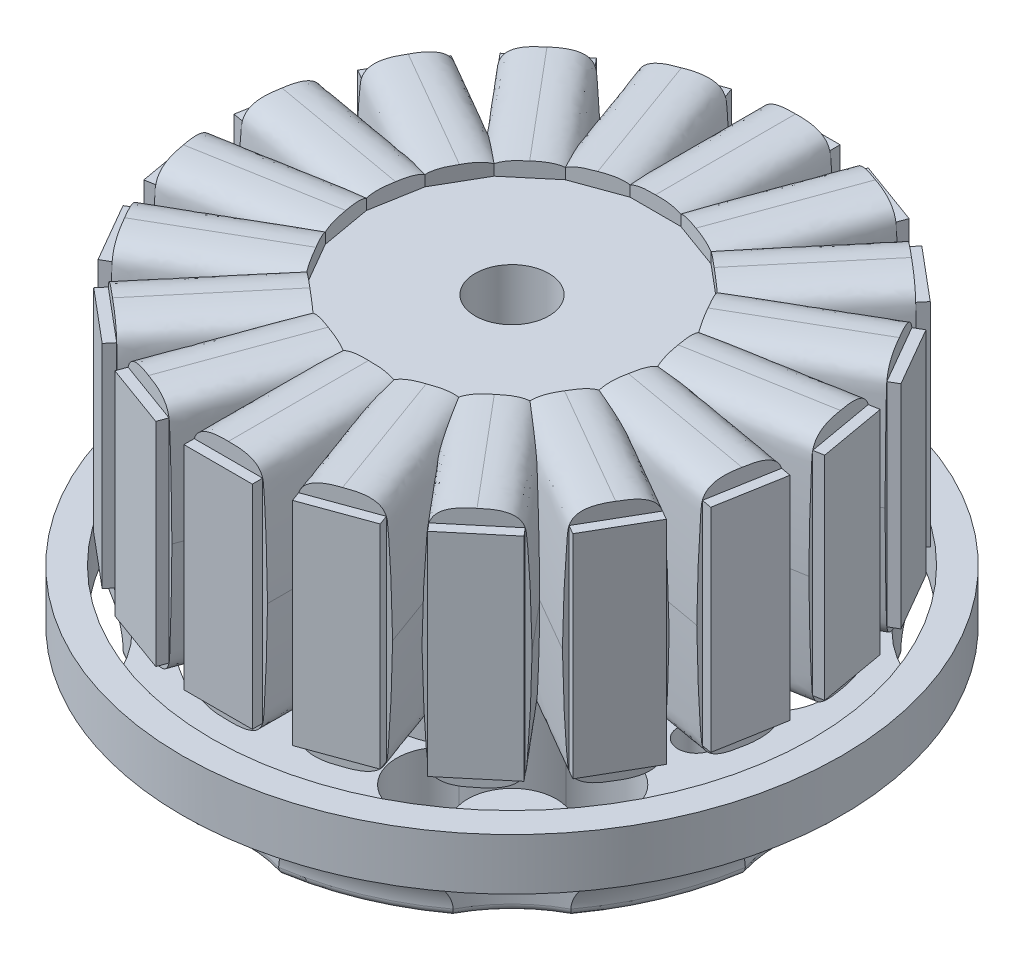
SolidWorks part; units mm, degrees
ref_plane "Front Plane" through (0, 0, 0) normal (0, 0, 1) x (1, 0, 0)
ref_plane "Top Plane" through (0, 0, 0) normal (0, 1, 0) x (1, 0, 0)
ref_plane "Right Plane" through (0, 0, 0) normal (1, 0, 0) x (0, 0, -1)
sketch "Sketch1" plane through (0, 0, 0) normal (0, 1, 0) x (1, 0, 0)
  circle A0 centre (0, 0) radius 22.36
  dimension "D1" = 44.72
extrude "Boss-Extrude1" add sketch "Sketch1" against normal blind 7.5
sketch "Sketch4" plane through (0, 0, 0) normal (0, 0, 1) x (1, 0, 0)
  line L0 (-22.36, 0) -> (-22.36, -7.5) construction
  line L1 (0, 0) -> (0, -7.5) construction
  line L2 (-22.36, -7.5) -> (22.36, -7.5) construction
  circle A0 centre (-22.36, -7) radius 3.5
  point P0 (-22.36, -3.5)
  dimension "D2" = 7
  dimension "D1" = 3.5
revolve "Cut-Revolve1" cut sketch "Sketch4" angle 360 about L1
sketch "Sketch6" plane through (0, 0, 0) normal (0, 1, 0) x (1, 0, 0)
  circle A0 centre (0, 0) radius 20.36
  circle A1 centre (0, 0) radius 22.36 construction
  dimension "D1" = 2
extrude "Cut-Extrude3" cut sketch "Sketch6" against normal offset from surface (3.9 mm away) 3.6 up to face at (0, -7.5, -18.8959)
sketch "Sketch7" plane through (0, -3.9, 0) normal (0, 1, 0) x (1, 0, 0)
  circle A0 centre (0, 0) radius 10
  dimension "D1" = 20
extrude "Boss-Extrude2" add sketch "Sketch7" along normal blind 20.8
sketch "Sketch9" plane through (0, 16.9, 0) normal (0, 1, 0) x (1, 0, 0)
  line L0 (0, 0) -> (0, 30.8814) construction
  line L2 (-2.32, 19.93) -> (2.32, 19.93)
  line L3 (-2.32, 19.93) -> (-2.32, 19.23)
  line L4 (-2.32, 19.23) -> (-0.3439, 19.23)
  line L5 (2.32, 19.93) -> (2.32, 19.23)
  line L6 (-2.32, 19.93) -> (2.32, 19.23) construction
  line L7 (-2.32, 19.23) -> (2.32, 19.93) construction
  line L16 (16.0999, 11.9742) -> (15.4937, 11.6242)
  line L75 (0.3439, 19.23) -> (2.32, 19.23)
  line L77 (-0.35, 19.23) -> (-0.35, 9.9939)
  line L79 (0.35, 19.23) -> (0.35, 9.9939)
  line L133 (-19.3407, 1.0545) -> (-18.9986, 2.9946) [skipped]
  line L134 (-20.0301, 1.1761) -> (-19.2244, 5.7456) [skipped]
  line L135 (-19.2244, 5.7456) -> (-18.535, 5.624) [skipped]
  line L136 (-20.0301, 1.1761) -> (-19.3407, 1.0545) [skipped]
  line L137 (-18.4199, 7.9558) -> (-17.8137, 7.6058) [skipped]
  line L138 (-18.4199, 7.9558) -> (-16.0999, 11.9742) [skipped]
  line L139 (-16.0999, 11.9742) -> (-15.4937, 11.6242) [skipped]
  line L140 (-17.8137, 7.6058) -> (-16.8287, 9.3119) [skipped]
  line L141 (-14.588, 13.776) -> (-14.138, 13.2398) [skipped]
  line L142 (-14.138, 13.2398) -> (-12.6289, 14.5061) [skipped]
  line L143 (-14.588, 13.776) -> (-11.0335, 16.7585) [skipped]
  line L144 (-11.0335, 16.7585) -> (-10.5836, 16.2223) [skipped]
  line L145 (-8.7571, 17.2768) -> (-6.9059, 17.9506) [skipped]
  line L146 (-8.9965, 17.9346) -> (-4.6364, 19.5216) [skipped]
  line L147 (-4.6364, 19.5216) -> (-4.397, 18.8638) [skipped]
  line L148 (-8.9965, 17.9346) -> (-8.7571, 17.2768) [skipped]
  line L161 (4.397, 18.8638) -> (6.2482, 18.19) [skipped]
  line L162 (4.6364, 19.5216) -> (8.9965, 17.9346) [skipped]
  line L163 (11.0335, 16.7585) -> (10.5836, 16.2223) [skipped]
  line L164 (11.0335, 16.7585) -> (14.588, 13.776) [skipped]
  line L165 (16.0999, 11.9742) -> (18.4199, 7.9558) [skipped]
  line L166 (18.4199, 7.9558) -> (17.8137, 7.6058) [skipped]
  line L167 (15.4937, 11.6242) -> (16.4787, 9.9181) [skipped]
  line L168 (19.2244, 5.7456) -> (18.535, 5.624) [skipped]
  line L169 (19.2244, 5.7456) -> (20.0301, 1.1761) [skipped]
  line L170 (19.3407, -1.0545) -> (18.9986, -2.9946) [skipped]
  line L171 (20.0301, -1.1761) -> (19.2244, -5.7456) [skipped]
  line L172 (19.2244, -5.7456) -> (18.535, -5.624) [skipped]
  line L187 (14.138, -13.2398) -> (12.6289, -14.5061) [skipped]
  line L188 (14.588, -13.776) -> (11.0335, -16.7585) [skipped]
  line L189 (18.4199, -7.9558) -> (16.0999, -11.9742) [skipped]
  line L190 (17.8137, -7.6058) -> (16.8287, -9.3119) [skipped]
  line L191 (16.0999, -11.9742) -> (15.4937, -11.6242) [skipped]
  line L192 (2.32, -19.23) -> (-2.32, -19.23) [skipped]
  line L193 (-2.32, -19.93) -> (-2.32, -19.23) [skipped]
  line L194 (-4.397, -18.8638) -> (-8.7571, -17.2768) [skipped]
  line L195 (-4.6364, -19.5216) -> (-8.9965, -17.9346) [skipped]
  line L196 (-11.0335, -16.7585) -> (-10.5836, -16.2223) [skipped]
  line L197 (-10.5836, -16.2223) -> (-14.138, -13.2398) [skipped]
  line L198 (-16.0999, -11.9742) -> (-18.4199, -7.9558) [skipped]
  line L199 (-19.2244, -5.7456) -> (-20.0301, -1.1761) [skipped]
  line L200 (-20.0301, -1.1761) -> (-19.3407, -1.0545) [skipped]
  line L201 (-18.535, -5.624) -> (-18.8771, -3.6839) [skipped]
  line L202 (-18.4199, -7.9558) -> (-17.8137, -7.6058) [skipped]
  line L203 (-15.4937, -11.6242) -> (-16.4787, -9.9181) [skipped]
  line L204 (-16.0999, -11.9742) -> (-15.4937, -11.6242) [skipped]
  line L205 (-14.588, -13.776) -> (-14.138, -13.2398) [skipped]
  line L206 (-11.0335, -16.7585) -> (-14.588, -13.776) [skipped]
  line L207 (-8.9965, -17.9346) -> (-8.7571, -17.2768) [skipped]
  line L208 (-19.2244, -5.7456) -> (-18.535, -5.624) [skipped]
  line L209 (-4.6364, -19.5216) -> (-4.397, -18.8638) [skipped]
  line L210 (2.32, -19.93) -> (-2.32, -19.93) [skipped]
  line L211 (2.32, -19.93) -> (2.32, -19.23) [skipped]
  line L212 (8.9965, -17.9346) -> (4.6364, -19.5216) [skipped]
  line L213 (8.7571, -17.2768) -> (4.397, -18.8638) [skipped]
  line L214 (4.7854, -19.9309) -> (4.397, -18.8638) [skipped]
  line L215 (11.0335, -16.7585) -> (10.5836, -16.2223) [skipped]
  line L216 (8.9965, -17.9346) -> (8.7571, -17.2768) [skipped]
  line L217 (14.588, -13.776) -> (14.138, -13.2398) [skipped]
  line L218 (18.4199, -7.9558) -> (17.8137, -7.6058) [skipped]
  line L219 (20.0301, -1.1761) -> (19.3407, -1.0545) [skipped]
  line L220 (20.0301, 1.1761) -> (19.3407, 1.0545) [skipped]
  line L221 (18.535, 5.624) -> (18.8771, 3.6839) [skipped]
  line L222 (4.6364, 19.5216) -> (4.397, 18.8638) [skipped]
  line L223 (8.9965, 17.9346) -> (8.7571, 17.2768) [skipped]
  line L224 (10.5836, 16.2223) -> (12.0927, 14.956) [skipped]
  line L225 (14.588, 13.776) -> (14.138, 13.2398) [skipped]
  arc A2 (0.35, 9.9939) -> (-0.35, 9.9939) centre (0, 0) ccw
  point P3 (0, 19.58)
  point P10 (0, 12.4867)
  point P79 (0, 0)
  point P156 (0, 0)
  dimension "D1" = 0.7
  dimension "D2" = 4.64
  dimension "D3" = 19.58
  dimension "D4" = 18
extrude "Boss-Extrude3" add sketch "Sketch9" against normal offset from surface (15.4 mm away) 1.5 up to face at (0, 0, 20.36)
pattern_circular "CirPattern1" count 18 over 360 about axis through (0, 0, 0) along (0, 1, 0) of "Boss-Extrude3"
sketch "Sketch10" plane through (0, 16.9, 0) normal (0, 1, 0) x (1, 0, 0)
  circle A0 centre (0, 0) radius 24.3732
extrude "Cut-Extrude4" cut sketch "Sketch10" against normal blind 1
sketch "Sketch11" plane through (0, -7.5, 0) normal (0, -1, 0) x (1, 0, 0)
  circle A0 centre (0, 0) radius 8
  dimension "D1" = 16
extrude "Cut-Extrude5" cut sketch "Sketch11" against normal blind 0.2
sketch "Sketch12" plane through (0, -7.3, 0) normal (0, -1, 0) x (-1, 0, 0)
  circle A0 centre (0, 0) radius 3.75
  circle A1 centre (0, 0) radius 2.5
  dimension "D1" = 7.5
  dimension "D2" = 5
extrude "Boss-Extrude4" add sketch "Sketch12" along normal blind 0.2
sketch "Sketch13" plane through (0, -7.3, 0) normal (0, -1, 0) x (1, 0, 0)
  circle A0 centre (0, 0) radius 2.5
extrude "Cut-Extrude6" cut sketch "Sketch13" against normal blind 41.2
sketch "Sketch14" plane through (0, -7.5, 0) normal (0, -1, 0) x (-1, 0, 0)
  line L0 (0, 0) -> (0, -25.6549) construction
  line L1 (0, 0) -> (-22.5396, -22.5396) construction
  line L2 (0, 0) -> (-26.5501, 0) construction
  circle A0 centre (0, -12.5) radius 1.25
  circle A1 centre (-12.5, 0) radius 1.25
  circle A2 centre (0, 12.5) radius 1.25
  circle A3 centre (12.5, 0) radius 1.25
  circle A4 centre (-11.3137, -11.3137) radius 1
  circle A5 centre (-4.1411, 15.4548) radius 1
  circle A6 centre (15.4548, -4.1411) radius 1
  circle A7 centre (0, 0) radius 22.36 construction
  circle A8 centre (-27.861, 0) radius 9.6379
  circle A9 centre (-19.7007, 19.7007) radius 9.6379
  circle A10 centre (0, 27.861) radius 9.6379
  circle A11 centre (19.7007, 19.7007) radius 9.6379
  circle A12 centre (27.861, 0) radius 9.6379
  circle A13 centre (19.7007, -19.7007) radius 9.6379
  circle A14 centre (0, -27.861) radius 9.6379
  circle A15 centre (-19.7007, -19.7007) radius 9.6379
  point P14 (0, 0)
  point P15 (-18.5, 0)
  point P16 (-19.8003, 10.3884)
  point P17 (-21.236, 7)
  point P22 (0, 0)
  point P24 (-21.236, -7)
  point P41 (0, 0)
  point P47 (0, 0)
  dimension "D1" = 2.5
  dimension "D5" = 2
  dimension "D2" = 12.5
  dimension "D4" = 45
  dimension "D6" = 16
  dimension "D8" = 18.5
  dimension "D9" = 7
  dimension "D10" = 7
  dimension "D12" = 3.68
  dimension "D3" = 4
  dimension "D7" = 3
  dimension "D11" = 8
extrude "Cut-Extrude7" cut sketch "Sketch14" against normal blind 4
sketch "Sketch15" plane through (0, -7.5, 0) normal (0, -1, 0) x (-1, 0, 0)
  line L0 (0, 0) -> (0, -18.223) construction
  line L1 (0, 0) -> (-11.3137, -11.3137) construction
  line L2 (0, 0) -> (-12.5, 0) construction
  line L3 (0, 0) -> (-4.1411, 15.4548) construction
  line L4 (0, 0) -> (10.251, -2.7468) construction
  line L5 (12.557, -3.3646) -> (15.4548, -4.1411) construction
  arc A0 (2.905, -18.6713) -> (-2.905, -18.6713) centre (0, -27.861) ccw construction
  arc A1 (-8.6571, -5.0055) -> (-5.0501, -8.6311) centre (0, 0) ccw
  arc A2 (10.6792, -3.4673) -> (8.6838, -4.959) centre (11.3975, -6.5086) ccw
  arc A3 (10.6792, -3.4673) -> (12.5009, -4.6651) centre (11.024, -4.9271) cw
  arc A4 (14.0447, 8.1737) -> (8.1473, 14.06) centre (0, 0) ccw
  arc A5 (12.5009, -4.6651) -> (13.5648, -6.4709) centre (15.4548, -4.1411) ccw
  arc A6 (4.9724, -8.6761) -> (8.0802, -14.0987) centre (6.5263, -11.3874) ccw
  arc A7 (8.0802, -14.0987) -> (13.9031, -8.4122) centre (0, 0) ccw
  circle A8 centre (0, -12.5) radius 3.55 construction
  arc A9 (-8.6761, 4.9724) -> (-14.0987, 8.0802) centre (-11.3874, 6.5263) cw
  circle A10 centre (0, 12.5) radius 3.55 construction
  circle A11 centre (-12.5, 0) radius 3.55 construction
  circle A12 centre (-4.1411, 15.4548) radius 3 construction
  arc A13 (-8.5024, -12.3608) -> (-12.3698, -8.5057) centre (-11.3137, -11.3137) ccw
  arc A14 (8.6429, 5.03) -> (14.0447, 8.1737) centre (11.3438, 6.6018) ccw
  arc A15 (8.1473, 14.06) -> (5.0137, 8.6523) centre (6.5805, 11.3562) ccw
  arc A16 (-8.6761, 4.9724) -> (-4.959, 8.6838) centre (0, 0) cw
  arc A17 (13.5648, -6.4709) -> (13.9031, -8.4122) centre (12.6198, -7.6357) cw
  arc A18 (-7.5291, -14.3207) -> (-5.0501, -8.6311) centre (-6.6283, -11.3284) ccw
  arc A19 (-8.6571, -5.0055) -> (-14.3152, -7.5929) centre (-11.3624, -6.5697) ccw
  arc A20 (-3.4673, 10.6792) -> (-4.959, 8.6838) centre (-6.5086, 11.3975) cw
  arc A21 (-3.4673, 10.6792) -> (-4.6651, 12.5009) centre (-4.9271, 11.024) ccw
  arc A22 (11.4264, -3.3838) -> (8.6838, -4.959) centre (11.3975, -6.5086) ccw
  arc A23 (-7.5291, -14.3207) -> (-8.5024, -12.3608) centre (-7.0967, -12.8844) cw
  arc A24 (-14.3152, -7.5929) -> (-12.3698, -8.5057) centre (-12.8979, -7.1018) ccw
  arc A25 (4.9724, -8.6761) -> (8.6838, -4.959) centre (0, 0) ccw
  arc A26 (8.6429, 5.03) -> (5.0137, 8.6523) centre (0, 0) ccw
  arc A27 (-4.6651, 12.5009) -> (-6.4709, 13.5648) centre (-4.1411, 15.4548) cw
  arc A28 (-6.4709, 13.5648) -> (-8.4122, 13.9031) centre (-7.6357, 12.6198) ccw
  arc A29 (-14.0987, 8.0802) -> (-8.4122, 13.9031) centre (0, 0) cw
  dimension "D1" = 1.5
  dimension "D2" = 32.5
  dimension "D3" = 7.1
  dimension "D4" = 6
  dimension "D5" = 6
  dimension "D6" = 6
  dimension "D7" = 1.5
  dimension "D8" = 1.5
extrude "Cut-Extrude8" cut sketch "Sketch15" against normal blind 10 contours A25 A6 A7 A17 A5 A3 A2 | A26 A14 A4 A15 | A29 A9 A16 A20 A21 A27 A28 | A19 A24 A13 A23 A18 A1
sketch "Sketch16" plane through (16.6537, 0, -9.615) normal (-0.866, 0, 0.5) x (0.5, 0, 0.866)
  line L0 (0, 0) -> (0, 19.8608) construction
  line L2 (0, 8.7) -> (-2.32, 8.7) construction
  line L3 (-2.32, 1.5) -> (-2.32, 15.9) construction
  line L4 (2.32, 15.9) -> (-2.32, 15.9) construction
  line L5 (0, 8.7) -> (-6.2589, 8.7) construction
  spline S0 degree 3 poles (0, 16.9) (-1.5748, 16.9453) (-2.3432, 16.2444) (-2.5141, 13.7773) (-2.6305, 11.0743) (-2.65, 8.7) knots 0 0 0 0 0.099934 0.155486 0.555519 0.555519 0.555519 0.555519
  spline S1 degree 3 poles (0, 0.5) (-1.5748, 0.4547) (-2.3432, 1.1556) (-2.5141, 3.6227) (-2.6305, 6.3257) (-2.65, 8.7) knots 0 0 0 0 0.099934 0.155486 0.555519 0.555519 0.555519 0.555519
  spline S2 degree 3 poles (0, 0.5) (1.5748, 0.4547) (2.3432, 1.1556) (2.5141, 3.6227) (2.6305, 6.3257) (2.65, 8.7) knots 0 0 0 0 0.099934 0.155486 0.555519 0.555519 0.555519 0.555519
  spline S3 degree 3 poles (0, 16.9) (1.5748, 16.9453) (2.3432, 16.2444) (2.5141, 13.7773) (2.6305, 11.0743) (2.65, 8.7) knots 0 0 0 0 0.099934 0.155486 0.555519 0.555519 0.555519 0.555519
  point P5 (-2.65, 8.7)
  point P6 (0, 16.9)
  point P7 (-2.32, 15.9)
  dimension "D1" = 1
  dimension "D2" = 2.65
extrude "Boss-Extrude5" add sketch "Sketch16" along normal blind 9.5
pattern_circular "CirPattern4" count 18 over 360 about axis through (0, 16.9, 0) along (0, -1, 0) of "Boss-Extrude5"
fillet "Fillet2" radius 0.5 16 edges at (-12.8856, -7.5, 12.8856) (0, -7.5, 18.223) (12.8856, -7.5, 12.8856) (18.223, -7.5, 0) (12.8856, -7.5, -12.8856) (0, -7.5, -18.223) (-12.8856, -7.5, -12.8856) (-18.223, -7.5, 0) (-17.4575, -7.5, 7.2311) (-17.4575, -7.5, -7.2311) (-7.2311, -7.5, -17.4575) (7.2311, -7.5, -17.4575) (17.4575, -7.5, -7.2311) (17.4575, -7.5, 7.2311) (-7.2311, -7.5, 17.4575) (7.2311, -7.5, 17.4575)
